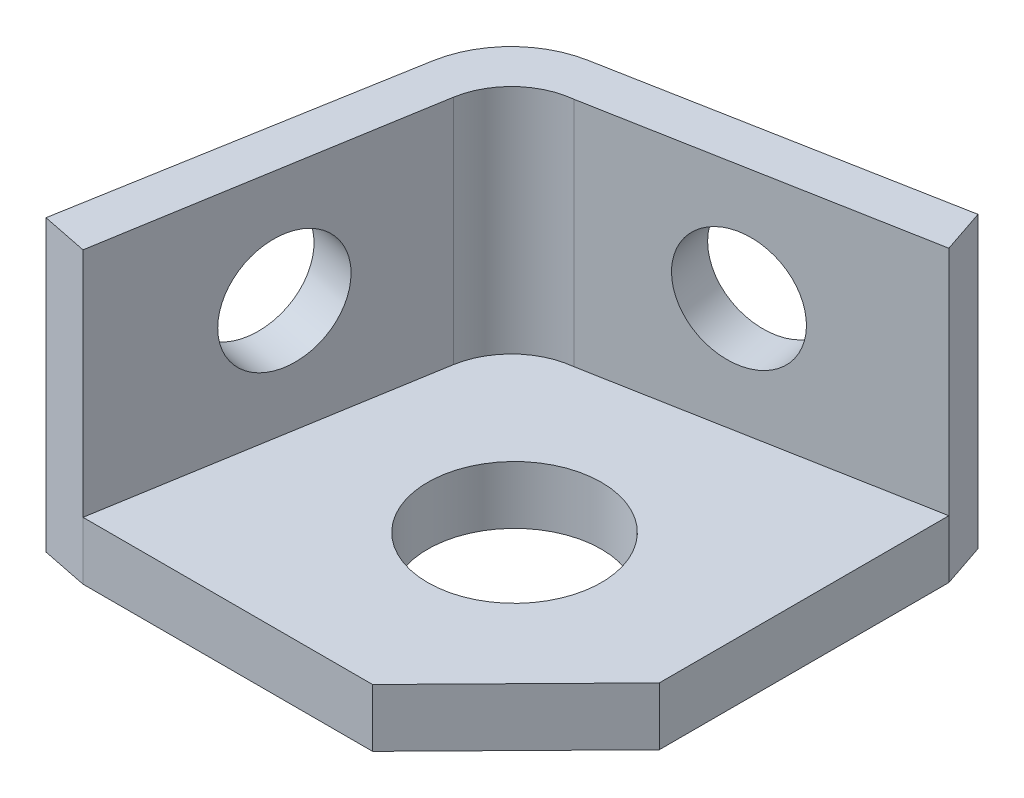
SolidWorks part; units mm, degrees
ref_plane "前视基准面" through (0, 0, 0) normal (0, 0, 1) x (1, 0, 0)
ref_plane "上视基准面" through (0, 0, 0) normal (0, 1, 0) x (1, 0, 0)
ref_plane "右视基准面" through (0, 0, 0) normal (1, 0, 0) x (0, 0, -1)
other "Configuration Table"
sketch "草图1" plane through (0, 0, 0) normal (0, 1, 0) x (1, 0, 0)
  line L0 (-37.7286, -22.3722) -> (12.2714, -22.3722)
  line L1 (36.7877, 2.6278) -> (36.7877, 52.6278)
  line L2 (-46.7464, 60.0249) -> (95.8055, -79.7692) construction
  line L3 (-37.7286, -22.3722) -> (-28.5766, 32.43)
  line L4 (12.2714, -22.3722) -> (36.7877, 2.6278)
  line L5 (36.7877, 52.6278) -> (-17.8494, 42.5372)
  line L6 (-37.7286, -22.3722) -> (-45.7286, -20.7608)
  line L7 (36.7877, 52.6278) -> (34.2345, 60.2095)
  line L8 (-45.7286, -20.7608) -> (-35.7991, 36.0866)
  line L9 (34.2345, 60.2095) -> (-22.4842, 49.5692)
  circle A0 centre (1.7877, 12.6278) radius 15
  arc A1 (-28.5766, 32.43) -> (-17.8494, 42.5372) centre (-16.5609, 30.4234) cw
  arc A2 (-35.7991, 36.0866) -> (-22.4842, 49.5692) centre (-19.4181, 33.2253) cw
  point P5 (12.2714, -22.3722)
  point P6 (36.7877, 2.6278)
  point P9 (24.5295, -9.8722)
  point P19 (0, 0)
  point P20 (0, 0)
  point P21 (0, 0)
  point P22 (0, 0)
  point P23 (0, 0)
  point P24 (0, 0)
  point P25 (0, 0)
  point P26 (0, 0)
  point P27 (0, 0)
  point P28 (0, 0)
  dimension "D6" = 8
  dimension "D8" = 60
  dimension "D1" = 35
  dimension "D2" = 35
  dimension "D3" = 50
  dimension "D4" = 50
  dimension "D5" = 25
  dimension "D7" = 8
extrude "凸台-拉伸1" add sketch "草图1" along normal blind 10 contours L2 A1 L3 L0 L4 A0 | A1 L2 A0 L4 L1 L5 region at (-13.2156, 0, 1.7767) region at (15.9984, 0, -27.7822)
extrude "凸台-拉伸2" add sketch "草图1<3>" along normal blind 50 contours L2 A2 L8 L6 L3 A1 | A2 L2 A1 L5 L7 L9 region at (-36.1648, 0, -10.5505) region at (3.0394, 0, -50.2889)
sketch "草图1<3>" plane through (0, 0, 0) normal (0, 1, 0) x (1, 0, 0) same geometry as "草图1"
sketch "草图3" plane through (-40.8558, 0, -7.1363) normal (-0.9851, 0, -0.1721) x (-0.1721, 0, 0.9851)
  line L0 (28.3195, 0) -> (-29.3886, 0) construction
  line L2 (28.3195, 50) -> (28.3195, 0) construction
  circle A0 centre (-1.6805, 30) radius 10
  point P6 (-28.4188, 22.2168)
  point P9 (-4.4406, 19.7904)
  dimension "D1" = 30
  dimension "D2" = 30
extrude "切除-拉伸1" cut sketch "草图3" against normal through all
sketch "草图4" plane through (-9.7473, 0, -51.9586) normal (-0.1844, 0, -0.9829) x (-0.9829, 0, 0.1844)
  line L0 (-44.749, 0) -> (12.959, 0) construction
  line L1 (-44.749, 50) -> (-44.749, 0) construction
  circle A0 centre (-14.749, 30) radius 10
  dimension "D1" = 30
  dimension "D2" = 30
extrude "切除-拉伸2" cut sketch "草图4" against normal through all
